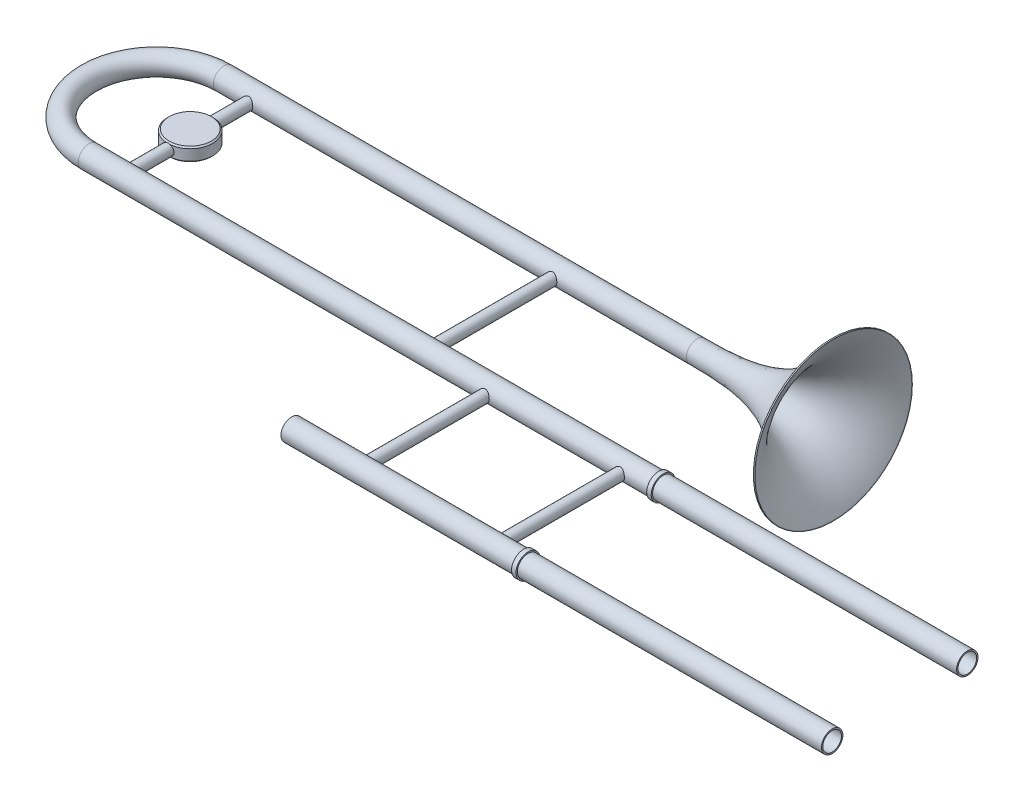
SolidWorks part; units mm, degrees
material "Brass"
ref_plane "Front Plane" through (0, 0, 0) normal (0, 0, 1) x (1, 0, 0)
ref_plane "Top Plane" through (0, 0, 0) normal (0, 1, 0) x (1, 0, 0)
ref_plane "Right Plane" through (0, 0, 0) normal (1, 0, 0) x (0, 0, -1)
sketch "Sketch1" plane through (0, 0, 0) normal (0, 1, 0) x (1, 0, 0)
  line L0 (102.9796, 140.2275) -> (-430.4204, 140.2275)
  line L2 (-430.4204, -12.1725) -> (560.1796, -12.1725)
  line L3 (560.1796, -12.1725) -> (560.1796, -164.5725) construction
  line L4 (560.1796, -164.5725) -> (-49.4204, -164.5725) construction
  line L5 (26.7796, -164.5725) -> (26.7796, -12.1725) construction
  line L6 (179.1796, -164.5725) -> (179.1796, -12.1725) construction
  line L7 (212.1996, 45.2818) -> (212.1996, -292.6275) construction
  line L8 (217.2796, 45.2818) -> (217.2796, -292.6275) construction
  line L9 (-392.3204, 140.2275) -> (-392.3204, -12.1725) construction
  line L10 (-49.4204, 140.2275) -> (-49.4204, -12.1725) construction
  arc A0 (-430.4204, 140.2275) -> (-430.4204, -12.1725) centre (-430.4204, 64.0275) ccw
  dimension "D9" = 990.6
  dimension "D1" = 609.6
  dimension "D2" = 76.2
  dimension "D3" = 152.4
  dimension "D4" = 5.08
  dimension "D5" = 342.9
  dimension "D6" = 76.2
  dimension "D7" = 152.4
  dimension "D8" = 342.9
  dimension "D10" = 152.4
  dimension "D11" = 152.4
sweep "Sweep-Thin1" add path "Sketch1" circular profile diameter 24.13 parameters "D1"=1.524, "D3"=24.13
sketch "Sketch22" plane through (0, 0, 0) normal (0, 1, 0) x (1, 0, 0)
  line L0 (-49.4204, -164.5725) -> (560.1796, -164.5725)
sweep "Sweep-Thin2" add path "Sketch22" circular profile diameter 24.13 parameters "D1"=1.524, "D3"=24.13
sketch "Sketch63" plane through (0, 0, 0) normal (0, 1, 0) x (1, 0, 0)
  line L0 (-392.3204, -12.1725) -> (-392.3204, 140.2275)
sweep "Sweep-Thin3" add path "Sketch63" circular profile diameter 12.7 parameters "D1"=1.524, "D3"=12.7
sketch "Sketch84" plane through (0, 0, 0) normal (0, 1, 0) x (1, 0, 0)
  line L0 (-49.4204, -12.1725) -> (-49.4204, 140.2275)
sweep "Sweep-Thin4" add path "Sketch84" circular profile diameter 12.7 parameters "D1"=1.524, "D3"=12.7
sketch "Sketch105" plane through (0, 0, 0) normal (0, 1, 0) x (1, 0, 0)
  line L0 (26.7796, -164.5725) -> (26.7796, -12.1725)
sweep "Sweep-Thin5" add path "Sketch105" circular profile diameter 12.7 parameters "D1"=1.524, "D3"=12.7
sketch "Sketch126" plane through (0, 0, 0) normal (0, 1, 0) x (1, 0, 0)
  line L0 (179.1796, -164.5725) -> (179.1796, -12.1725)
sweep "Sweep-Thin6" add path "Sketch126" circular profile diameter 12.7 parameters "D1"=1.524, "D3"=12.7
sketch "Sketch147" plane through (560.1796, 0, 0) normal (1, 0, 0) x (0, 0, -1)
  line L2 (-12.1725, -6.35) -> (-12.1725, 6.35) construction
  circle A0 centre (-164.5725, 0) radius 10.541
  circle A2 centre (140.2275, 0) radius 10.541
  circle A3 centre (140.2275, 0) radius 10.541 construction
  circle A4 centre (-12.1725, 0) radius 10.541
  circle A5 centre (-12.1725, 0) radius 10.541 construction
  circle A6 centre (-164.5725, 0) radius 10.541 construction
extrude "Cut-Extrude1" cut sketch "Sketch147" against normal blind 965.2 contours A4 | A2 | A0 region at (560.1796, 0, -140.2275) region at (560.1796, 0, 12.1725)
sketch3d "3DSketch1"
  line L0 (217.2796, 0, 292.6275) -> (217.2796, 55.5811, 292.6275) construction
  line L1 (217.2796, 0, 292.6275) -> (266.8667, 0, 292.6275) construction
ref_plane "Plane1" through (217.2796, 0, 0) normal (1, 0, 0) x (0, 0, -1)
sketch "Sketch148" plane through (217.2796, 0, 0) normal (1, 0, 0) x (0, 0, -1)
  line L0 (140.2275, 0) -> (-12.1725, 0) construction
  line L1 (140.2275, 0) -> (-12.1725, 0) construction
  circle A0 centre (-164.5725, 0) radius 12.065
  circle A1 centre (-164.5725, 0) radius 12.065 construction
  circle A2 centre (-164.5725, 0) radius 13.589
  circle A3 centre (-12.1725, 0) radius 12.065
  circle A4 centre (-12.1725, 0) radius 12.065 construction
  circle A5 centre (-12.1725, 0) radius 13.589
  dimension "D1" = 27.178
  dimension "D2" = 27.178
extrude "Boss-Extrude1" add sketch "Sketch148" against normal blind 5.08
sketch "Sketch149" plane through (0, 0, 0) normal (0, 1, 0) x (1, 0, 0)
  line L0 (102.9796, 140.2275) -> (102.9796, 152.2925) construction
  line L1 (120.1083, 152.2925) -> (85.8508, 152.2925) construction
  line L3 (102.9796, 140.2275) -> (-430.4204, 140.2275) construction
  line L7 (255.3796, 229.1275) -> (256.9036, 229.1275)
  line L8 (256.9036, 229.1275) -> (256.7789, 228.5238)
  line L9 (102.9796, 150.7685) -> (102.9796, 152.2925)
  spline S0 degree 3 poles (102.9796, 152.2925) (132.4492, 152.2925) (199.0284, 153.3834) (243.6128, 201.8492) (255.3796, 229.1275) knots 0 0 0 0 0.508018 1 1 1 1
  spline S1 degree 1 poles (102.9796, 150.7685) (256.7789, 228.5238) knots 0 0 1 1 construction
  spline S2 degree 3 poles (102.9796, 150.7685) (104.8099, 150.7685) (108.4484, 150.7727) (115.9036, 150.8196) (125.3897, 150.9916) (136.9693, 151.5108) (152.5078, 152.7958) (171.8411, 155.8474) (194.0279, 162.8842) (214.2097, 174.4274) (231.8045, 189.714) (243.9446, 204.8917) (251.9097, 218.1181) (255.2613, 225.0057) (256.7789, 228.5238) knots 0 0 0 0 0.03125 0.0625 0.125 0.1875 0.25 0.375 0.5 0.625 0.75 0.875 0.9375 1 1 1 1
  dimension "D1" = 12.065
  dimension "D2" = 91.44
  dimension "D3" = 127
  dimension "D4" = 152.4
  dimension "D5" = 25.4
  dimension "D6" = 50.8
  dimension "D7" = 88.9
  dimension "D8" = 1.524
  dimension "D9" = 1.524
revolve "Revolve1" add sketch "Sketch149" angle 360 about L0
sketch "Sketch150" plane through (0, 0, 0) normal (0, 1, 0) x (1, 0, 0)
  line L0 (-392.3204, 140.2275) -> (-392.3204, -12.1725) construction
  circle A0 centre (-392.3204, 64.0275) radius 25.4
  point P4 (0, 0)
  dimension "D1" = 50.8
extrude "Boss-Extrude2" add sketch "Sketch150" along normal blind 7.62 and the other way blind 7.62
chamfer "Chamfer1" distance 1.524 angle 45 2 edges at (-392.3204, -7.62, -38.6275) (-392.3204, 7.62, -38.6275)
